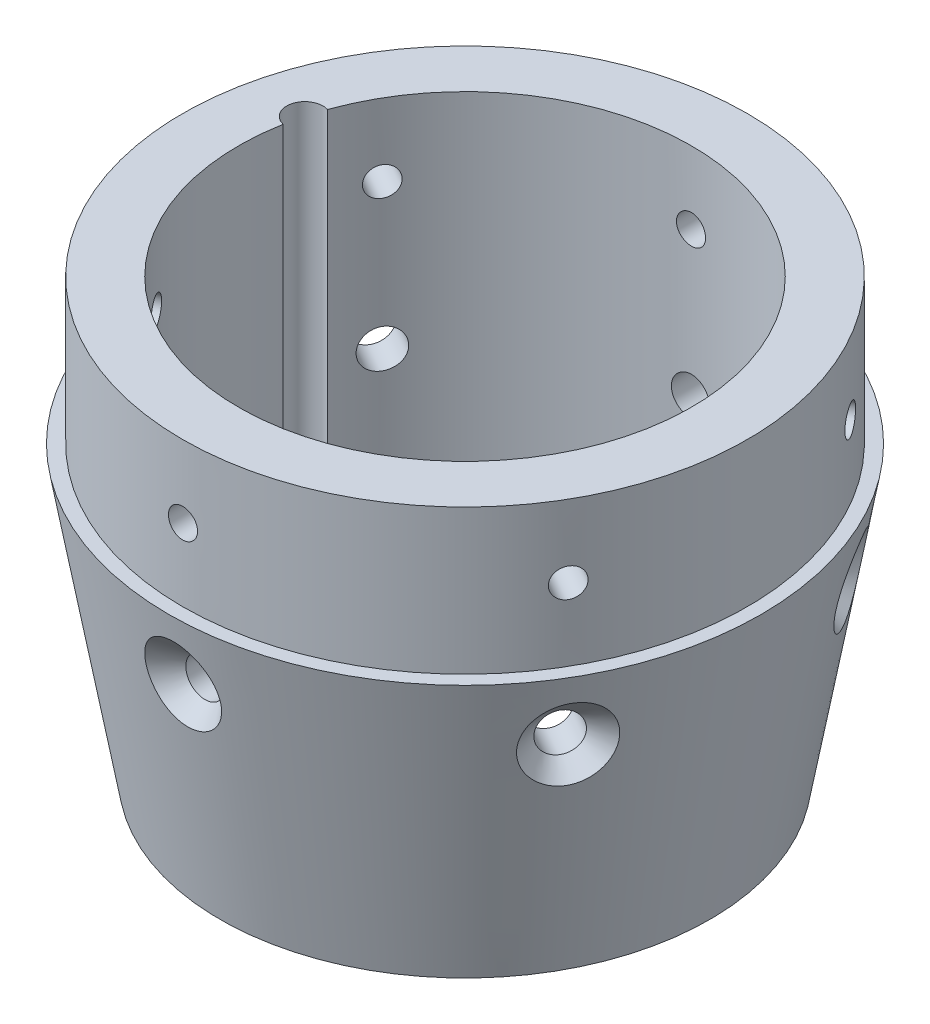
SolidWorks part; units mm, degrees
material "6061-T6 (SS)"
ref_plane "Front Plane" through (0, 0, 0) normal (0, 0, 1) x (1, 0, 0)
ref_plane "Top Plane" through (0, 0, 0) normal (0, 1, 0) x (1, 0, 0)
ref_plane "Right Plane" through (0, 0, 0) normal (1, 0, 0) x (0, 0, -1)
sketch "Sketch1" plane through (0, 0, 0) normal (0, 0, 1) x (1, 0, 0)
  line L2 (-51.9176, 50.8) -> (-49.53, 50.8)
  line L3 (-49.53, 50.8) -> (-49.53, 76.2)
  line L4 (-49.53, 76.2) -> (-39.7256, 76.2)
  line L5 (-39.7256, 76.2) -> (-39.7256, 0)
  line L6 (-39.7256, 0) -> (0, 0) construction
  line L7 (0, 0) -> (0, 68.3515) construction
  line L8 (-39.7256, 0) -> (-42.9602, 0)
  line L9 (-42.9602, 0) -> (-51.9176, 50.8)
  dimension "D1" = 49.53
  dimension "D2" = 51.9176
  dimension "D3" = 39.7256
  dimension "D4" = 10
  dimension "D5" = 25.4
  dimension "D6" = 50.8
revolve "Revolve1" add sketch "Sketch1" angle 360 about L7
ref_plane "Plane1" through (0, 0, 49.53) normal (0, 0, 1) x (1, 0, 0)
hole_wizard "Tap Drill for 1/4-20 Tap1" positions "Sketch4" profile "Sketch5" hole size "1/4-20" standard "ANSI Inch" end condition up to next
sketch "Sketch4" plane through (0, 0, 49.53) normal (0, 0, 1) x (1, 0, 0)
  line L3 (0, 76.2) -> (0, 50.8) construction
  line L4 (39.7256, 76.2) -> (-39.7256, 76.2) construction
  line L5 (51.9176, 50.8) -> (-51.9176, 50.8) construction
  point P9 (0, 63.5)
  point P26 (0, 63.5)
sketch "Sketch5" plane through (0, 63.5, 49.53) normal (1, 0, 0) x (0, -1, 0)
  line L0 (0, 0) -> (0, 9.8044)
  line L1 (0, 9.8044) -> (2.5527, 9.8044)
  line L2 (2.5527, 9.8044) -> (2.5527, 0)
  line L5 (2.5527, 0) -> (0, 0)
  line L11 (0, -6.35) -> (0, 107.95) construction
  dimension "Thru Hole Dia." = 5.1054
  dimension "Thru Hole Depth" = 9.8044
pattern_circular "CirPattern1" count 6 over 360 about axis through (0, 0, 0) along (0, -1, 0) of "Tap Drill for 1/4-20 Tap1"
sketch "Sketch6" plane through (0, 0, 0) normal (1, 0, 0) x (0, 0, -1)
  line L0 (0, 0) -> (42.9602, 0) construction
  line L1 (42.9602, 0) -> (49.1184, 34.925) construction
  line L3 (42.9602, 0) -> (51.9176, 50.8) construction
  point P7 (49.1184, 34.925)
  dimension "D1" = 34.925
ref_plane "Plane2" through (0, 0, -49.1184) normal (0, 0, 1) x (1, 0, 0)
hole_wizard "CSK for 1/4 Flat Head Machine Screw1" positions "Sketch7" profile "Sketch9" countersink size "1/4" standard "ANSI Inch" end condition up to next
sketch "Sketch7" plane through (0, 0, -49.1184) normal (0, 0, 1) x (1, 0, 0)
  line L0 (51.9176, 50.8) -> (-51.9176, 50.8) construction
  point P0 (0, 38.1)
  dimension "D1" = 12.7
sketch "Sketch9" plane through (0, 38.1, -49.1184) normal (1, 0, 0) x (0, 1, 0)
  line L0 (0, 0) -> (0, 9.3928)
  line L1 (0, 9.3928) -> (3.3782, 9.3928)
  line L2 (3.3782, 9.3928) -> (3.3782, 3.5209)
  line L3 (3.3782, 3.5209) -> (6.4389, 0)
  line L5 (6.4389, 0) -> (0, 0)
  line L6 (-3.3782, 3.5209) -> (-6.4389, 0) construction
  line L11 (0, -6.35) -> (0, 107.95) construction
  dimension "Thru Hole Dia." = 6.7564
  dimension "Thru Hole Depth" = 9.3928
  dimension "Near C'Sink Dia." = 12.8778
  dimension "Near C'Sink Angle" = 82
sketch "Sketch12" plane through (0, 76.2, 0) normal (0, 1, 0) x (1, 0, 0)
  line L0 (0, 0) -> (-38.372, 10.2817) construction
  line L1 (-38.372, 10.2817) -> (-38.372, 0) construction
  line L2 (-38.372, 0) -> (0, 0) construction
  circle A0 centre (-38.372, 10.2817) radius 3.175
  circle A6 centre (0, 0) radius 39.7256 construction
  dimension "D1" = 6.35
  dimension "D2" = 15
extrude "Cut-Extrude2" cut sketch "Sketch12" against normal through all
sketch "Sketch13" plane through (0, 0, 0) normal (1, 0, 0) x (0, 0, -1)
  line L0 (0, 0) -> (39.6875, 0) construction
  line L1 (-39.7256, 0) -> (39.7256, 0) construction
  line L2 (-42.9602, 0) -> (42.9602, 0) construction
  line L3 (39.6875, 0) -> (39.6875, 38.1) construction
  line L4 (39.6875, 38.1) -> (45.5975, 38.1) construction
  line L5 (45.5975, 41.4782) -> (45.5975, 34.7218) construction
  line L6 (45.5975, 38.1) -> (45.5975, 41.4782) construction
  line L7 (45.5975, 41.4782) -> (49.1184, 44.5389) construction
  line L8 (49.1184, 44.5389) -> (52.2934, 47.2989)
  line L9 (49.1184, 44.5389) -> (49.1184, 38.1)
  line L10 (49.1184, 44.5389) -> (49.1184, 37.2687) construction
  line L11 (49.1184, 38.1) -> (52.2934, 38.1)
  line L12 (52.2934, 38.1) -> (52.2934, 47.2989)
  dimension "D1" = 3.3782
  dimension "D2" = 41
  dimension "D3" = 3.175
  dimension "D4" = 39.6875
revolve "Cut-Revolve1" cut sketch "Sketch13" angle 360 about L4
pattern_circular "CirPattern2" count 6 over 360 about axis through (0, 0, 0) along (0, -1, 0) of "CSK for 1/4 Flat Head Machine Screw1", "Cut-Revolve1" reverse direction yes
